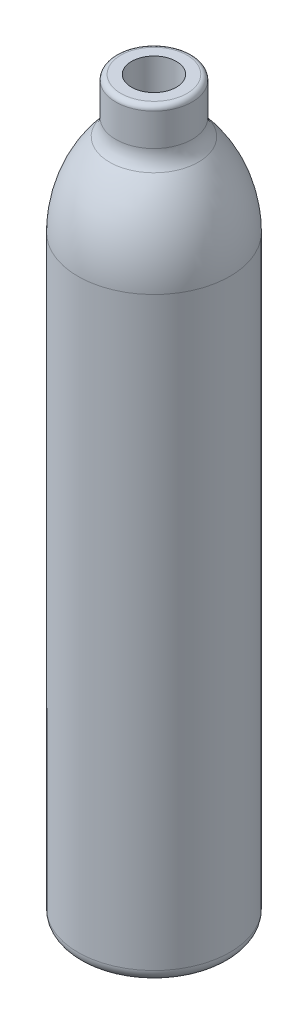
SolidWorks part; units mm, degrees
ref_plane "前视基准面" through (0, 0, 0) normal (0, 0, 1) x (1, 0, 0)
ref_plane "上视基准面" through (0, 0, 0) normal (0, 1, 0) x (1, 0, 0)
ref_plane "右视基准面" through (0, 0, 0) normal (1, 0, 0) x (0, 0, -1)
sketch "草图1" plane through (0, 0, 0) normal (0, 0, 1) x (1, 0, 0)
  line L0 (0, 129.3029) -> (0, -165.6971)
  line L1 (15.3, 127.3029) -> (15.3, 114.3029)
  line L2 (30.5, 74.3029) -> (30.5, -160.6971)
  line L3 (25.5, -165.6971) -> (0, -165.6971)
  line L4 (13.3, 129.3029) -> (0, 129.3029)
  arc A0 (15.3, 114.3029) -> (17.8236, 107.6618) centre (25.3, 114.3029) ccw
  arc A1 (17.8236, 107.6618) -> (30.5, 74.3029) centre (-19.7316, 74.3029) cw
  arc A2 (15.3, 127.3029) -> (13.3, 129.3029) centre (13.3, 127.3029) ccw
  arc A3 (30.5, -160.6971) -> (25.5, -165.6971) centre (25.5, -160.6971) cw
  point P9 (15.3, 129.3029)
  point P12 (30.5, -165.6971)
  dimension "D6" = 10
  dimension "D7" = 2
  dimension "D8" = 5
  dimension "D1" = 295
  dimension "D2" = 30.5
  dimension "D3" = 15.3
  dimension "D4" = 15
  dimension "D5" = 240
revolve "旋转1" add sketch "草图1" angle 360 about L0
shell "抽壳1" thickness 6.3 removed face at (-13.3, 129.3029, 0)
